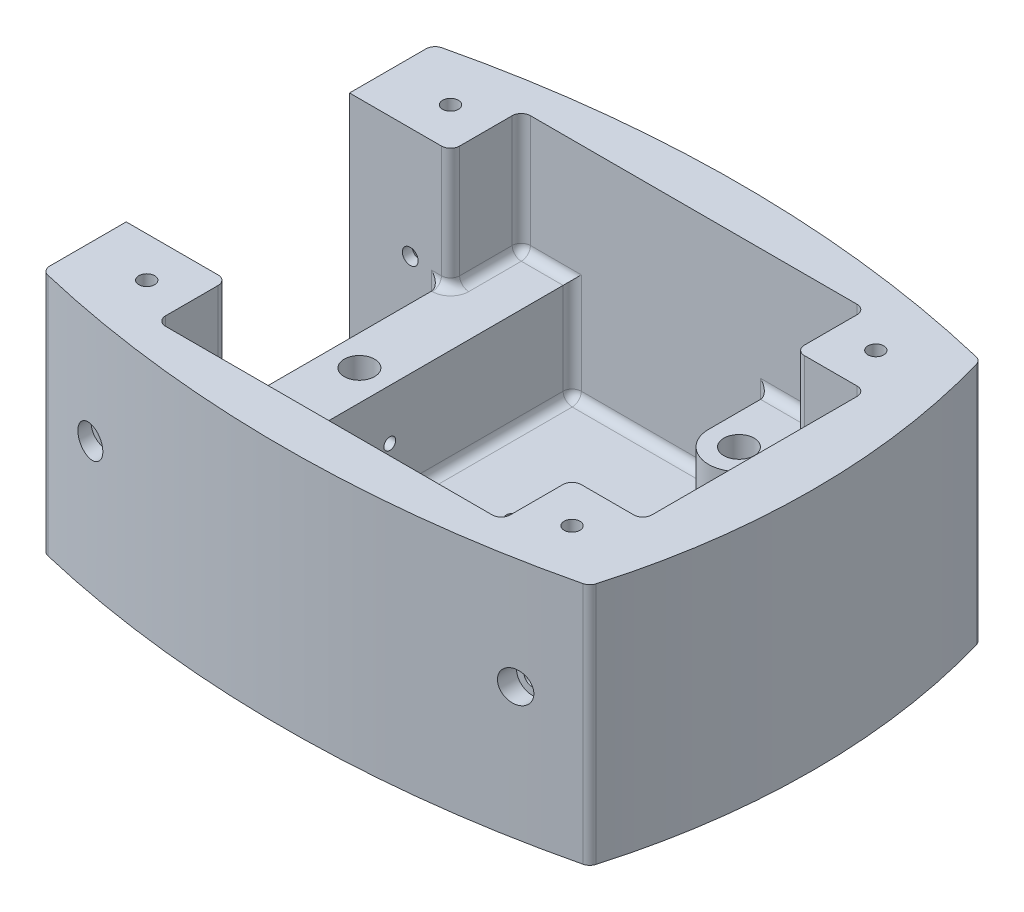
SolidWorks part; units mm, degrees
ref_plane "Front Plane" through (0, 0, 0) normal (0, 0, 1) x (1, 0, 0)
ref_plane "Top Plane" through (0, 0, 0) normal (0, 1, 0) x (1, 0, 0)
ref_plane "Right Plane" through (0, 0, 0) normal (1, 0, 0) x (0, 0, -1)
sketch "Sketch1" plane through (0, 0, 0) normal (0, 1, 0) x (1, 0, 0)
  line L0 (-140, 0) -> (0, 0) construction
  line L1 (-150.05, 10.05) -> (-129.95, 10.05)
  line L2 (-150.05, 10.05) -> (-150.05, -10.05)
  line L3 (-150.05, -10.05) -> (-129.95, -10.05)
  line L4 (-129.95, 10.05) -> (-129.95, -10.05)
  line L5 (-150.05, 10.05) -> (-129.95, -10.05) construction
  line L6 (-150.05, -10.05) -> (-129.95, 10.05) construction
  line L7 (-10.05, 10.05) -> (10.05, 10.05)
  line L8 (-10.05, 10.05) -> (-10.05, -10.05)
  line L9 (-10.05, -10.05) -> (10.05, -10.05)
  line L10 (10.05, 10.05) -> (10.05, -10.05)
  line L11 (-10.05, 10.05) -> (10.05, -10.05) construction
  line L12 (-10.05, -10.05) -> (10.05, 10.05) construction
  line L17 (-160, 14.2857) -> (-70, -50) construction
  line L18 (-150.05, -110.05) -> (-129.95, -110.05)
  line L23 (-150.05, -110.05) -> (-150.05, -89.95)
  line L24 (-150.05, -89.95) -> (-129.95, -89.95)
  line L25 (-129.95, -110.05) -> (-129.95, -89.95)
  line L26 (-150.05, -110.05) -> (-129.95, -89.95) construction
  line L27 (-150.05, -89.95) -> (-129.95, -110.05) construction
  line L28 (-10.05, -110.05) -> (10.05, -110.05)
  line L29 (-10.05, -110.05) -> (-10.05, -89.95)
  line L30 (-10.05, -89.95) -> (10.05, -89.95)
  line L31 (10.05, -110.05) -> (10.05, -89.95)
  line L32 (-10.05, -110.05) -> (10.05, -89.95) construction
  line L33 (-10.05, -89.95) -> (10.05, -110.05) construction
  line L35 (-70, -50) -> (20, -114.2857) construction
  line L37 (20, 14.2857) -> (-70, -50) construction
  line L38 (-70, -50) -> (-160, -114.2857) construction
  line L39 (-126.75, 10.05) -> (-126.75, -13.25)
  line L40 (-126.75, -13.25) -> (-150.05, -13.25)
  line L41 (-13.25, 10.05) -> (-13.25, -13.25)
  line L42 (-150.05, -86.75) -> (-126.75, -86.75)
  line L43 (-126.75, -86.75) -> (-126.75, -110.05)
  line L44 (-13.25, -13.25) -> (10.05, -13.25)
  line L45 (-13.25, -110.05) -> (-13.25, -86.75)
  line L46 (-13.25, -86.75) -> (10.05, -86.75)
  line L47 (10.05, -13.25) -> (10.05, -86.75)
  line L48 (-126.75, -110.05) -> (-13.25, -110.05)
  line L49 (-126.75, 10.05) -> (-13.25, 10.05)
  line L50 (-150.05, -13.25) -> (-150.05, -86.75)
  line L51 (-160, 14.2857) -> (-160, -114.2857)
  line L52 (-70, -50) -> (-54.5, -34.5) construction
  line L53 (-70, -50) -> (-85.5, -65.5) construction
  line L54 (-70, -50) -> (-54.5, -65.5) construction
  line L55 (-70, -50) -> (-85.5, -34.5) construction
  line L86 (-70, -50) -> (-55.1332, -66.9694) construction
  line L87 (-70, -50) -> (-55.1332, -33.0306) construction
  line L88 (-38.2949, -86.1892) -> (-35, -89.95) construction
  line L89 (-38.2949, -13.8108) -> (-35, -10.05) construction
  line L90 (-45, -89.95) -> (-45, -110.05)
  line L91 (-25, -89.95) -> (-25, -110.05)
  line L92 (-45, -10.05) -> (-45, 10.05)
  line L93 (-25, -10.05) -> (-25, 10.05)
  line L94 (-130, -13.25) -> (-130, -86.75)
  line L95 (-110, 10.05) -> (-110, -110.05)
  line L97 (-150.05, -13.25) -> (-160, -13.25)
  line L98 (-150.05, -86.75) -> (-160, -86.75)
  circle A2 centre (-120, -50) radius 5
  arc A5 (-160, 14.2857) -> (20, 14.2857) centre (-70, -354.9026) cw
  arc A6 (-160, -114.2857) -> (20, -114.2857) centre (-70, 254.9026) ccw
  arc A8 (20, 14.2857) -> (20, -114.2857) centre (-195.6208, -50) cw
  circle A9 centre (-70, -50) radius 14
  circle A10 centre (-35, -10.05) radius 5
  circle A11 centre (-35, -89.95) radius 5
  circle A16 centre (-85.5, -34.5) radius 1.6
  circle A17 centre (-54.5, -34.5) radius 1.6
  circle A18 centre (-85.5, -65.5) radius 1.6
  circle A19 centre (-54.5, -65.5) radius 1.6
  circle A20 centre (-140, 0) radius 2.6
  circle A21 centre (0, 0) radius 2.6
  circle A22 centre (0, -100) radius 2.6
  circle A23 centre (-140, -100) radius 2.6
  arc A42 (-45, -10.05) -> (-25, -10.05) centre (-35, -10.05) ccw
  arc A43 (-25, -89.95) -> (-45, -89.95) centre (-35, -89.95) ccw
  point P0 (-140, 0)
  point P5 (0, 0)
  point P10 (0, -100)
  point P16 (-140, -100)
  dimension "D4" = 28
  dimension "D5" = 31
  dimension "D7" = 225
  dimension "D8" = 380
  dimension "D9" = 10
  dimension "D16" = 3.2
  dimension "D17" = 5.2
  dimension "D19" = 10
  dimension "D18" = 20
  dimension "D20" = 10
  dimension "D1" = 20.1
  dimension "D2" = 140
  dimension "D3" = 100
  dimension "D6" = 180
  dimension "D10" = 35
  dimension "D11" = 3.2
  dimension "D12" = 3.2
  dimension "D13" = 3.2
  dimension "D14" = 3.2
  dimension "D15" = 20
extrude "Boss-Extrude1" add sketch "Sketch1" along normal blind 80 contours A8 A5 L51 A6 A9 A10 A11 A2 L31 L28 L29 L30 L25 L18 L23 L24 L1 L4 L3 L2 L7 L10 L9 L8 region at (-129.1671, 0, 1.6)
extrude "Boss-Extrude9" add sketch "Sketch1<7>" along normal blind 6.825 contours L40 L50 L42 L43 L48 L45 L46 L47 L44 L41 L49 L39 A19 A18 A17 A16 A9 | A2 | A10 | A11 | L50 | L98 L50 L97 L51 region at (-118.375, 0, -8.8325) region at (-54.8422, 0, 50) region at (-140.025, 0, 50) region at (-35, 0, 3.0299) region at (-155.025, 0, 50) region at (-35, 0, 96.9701)
sketch "Sketch1<7>" plane through (0, 0, 0) normal (0, 1, 0) x (1, 0, 0) same geometry as "Sketch1"
sketch "Sketch2" plane through (0, 0, 13.25) normal (0, 0, 1) x (1, 0, 0)
  line L0 (-150.05, 80) -> (-129.95, 80) construction
  line L1 (-126.75, 80) -> (-160, 80) construction
  line L2 (-129.95, 80) -> (-129.95, 6.825) construction
  line L3 (-150.05, 80) -> (-129.95, 6.825) construction
  line L4 (-129.95, 80) -> (-129.95, 0) construction
  line L5 (-129.95, 6.825) -> (-150.05, 6.825) construction
  line L6 (-150.05, 80) -> (-150.05, 0) construction
  line L7 (-150.05, 6.825) -> (-150.05, 80) construction
  line L8 (-10.05, 80) -> (10.05, 80) construction
  line L9 (10.05, 80) -> (10.05, 6.825) construction
  line L10 (10.05, 6.825) -> (-10.05, 6.825) construction
  line L11 (-10.05, 6.825) -> (-10.05, 80) construction
  line L12 (-129.95, 80) -> (-150.05, 6.825) construction
  line L13 (10.05, 80) -> (-10.05, 6.825) construction
  line L14 (-10.05, 80) -> (10.05, 6.825) construction
  line L15 (-126.75, 6.825) -> (-160, 6.825) construction
  circle A0 centre (-140, 43.4125) radius 2.6
  circle A2 centre (0, 43.4125) radius 2.6
  circle A5 centre (0, 43.4125) radius 5.05
  circle A6 centre (-140, 43.4125) radius 5.05
  dimension "D1" = 5.2
  dimension "D2" = 10.1
extrude "Cut-Extrude1" cut sketch "Sketch2" against normal blind 62 contours A6 A0 | A0 | A5 A2 | A2 region at (-140, 43.4125, 13.25) region at (0, 43.4125, 13.25) region at (-4.9072, 43.4125, 13.25) region at (-144.9072, 43.4125, 13.25)
extrude "Boss-Extrude5" add sketch "Sketch2<3>" against normal blind 26.5
sketch "Sketch2<3>" plane through (0, 0, 13.25) normal (0, 0, 1) x (1, 0, 0) same geometry as "Sketch2"
extrude "Cut-Extrude2" cut sketch "Sketch2<4>" against normal up to surface (23.3 mm away) up to face at (-145.05, 43.4125, -10.05)
sketch "Sketch2<4>" plane through (0, 0, 13.25) normal (0, 0, 1) x (1, 0, 0) same geometry as "Sketch2"
extrude "Boss-Extrude6" add sketch "Sketch2<5>" against normal up to surface (3.2 mm away) up to face at (-145.05, 43.4125, 10.05)
sketch "Sketch2<5>" plane through (0, 0, 13.25) normal (0, 0, 1) x (1, 0, 0) same geometry as "Sketch2"
extrude "Cut-Extrude3" cut sketch "Sketch2<6>" along normal blind 127.2 contours A6 A0 | A5 A2 | A2 | A0 region at (-140, 43.4125, 13.25) region at (0, 43.4125, 13.25) region at (-4.9072, 43.4125, 13.25) region at (-144.9072, 43.4125, 13.25)
sketch "Sketch2<6>" plane through (0, 0, 13.25) normal (0, 0, 1) x (1, 0, 0) same geometry as "Sketch2"
extrude "Boss-Extrude7" add sketch "Sketch2<7>" along normal blind 100 contours A6 A0 | A5 A2 region at (-4.9072, 43.4125, 13.25) region at (-144.9072, 43.4125, 13.25)
sketch "Sketch2<7>" plane through (0, 0, 13.25) normal (0, 0, 1) x (1, 0, 0) same geometry as "Sketch2"
extrude "Cut-Extrude4" cut sketch "Sketch2<8>" along normal up to surface (96.8 mm away) up to face at (-145.05, 43.4125, 110.05)
sketch "Sketch2<8>" plane through (0, 0, 13.25) normal (0, 0, 1) x (1, 0, 0) same geometry as "Sketch2"
extrude "Boss-Extrude8" add sketch "Sketch2<9>" along normal up to surface (76.7 mm away) up to face at (-145.05, 43.4125, 89.95)
sketch "Sketch2<9>" plane through (0, 0, 13.25) normal (0, 0, 1) x (1, 0, 0) same geometry as "Sketch2"
extrude "Cut-Extrude5" cut sketch "Sketch2<10>" along normal up to surface (73.5 mm away) contours A6 A0 | A0 | A5 A2 | A2 region at (-140, 43.4125, 13.25) region at (0, 43.4125, 13.25) region at (-4.9072, 43.4125, 13.25) region at (-144.9072, 43.4125, 13.25) up to face at (-5.05, 43.4125, 86.75)
sketch "Sketch2<10>" plane through (0, 0, 13.25) normal (0, 0, 1) x (1, 0, 0) same geometry as "Sketch2"
extrude "Boss-Extrude10" add sketch "Sketch1<9>" along normal blind 80 contours L18 L25 L24 L23 | L4 L1 L2 L3 | L28 L31 L30 L29 | L10 L7 L8 L9 region at (-140, 0, -9.7657) region at (0, 0, -9.7657) region at (-149.7657, 0, 100) region at (-9.7657, 0, 100)
sketch "Sketch1<9>" plane through (0, 0, 0) normal (0, 1, 0) x (1, 0, 0) same geometry as "Sketch1"
extrude "Cut-Extrude7" cut sketch "Sketch1<10>" along normal blind 61.9 contours L18 L25 L24 L23 | L4 L1 L2 L3 | L28 L31 L30 L29 | L10 L7 L8 L9 region at (-140, 0, -9.7657) region at (0, 0, -9.7657) region at (-149.7657, 0, 100) region at (-9.7657, 0, 100)
sketch "Sketch1<10>" plane through (0, 0, 0) normal (0, 1, 0) x (1, 0, 0) same geometry as "Sketch1"
extrude "Boss-Extrude11" add sketch "Sketch1<11>" along normal blind 40 contours A2 | A10 | A11 region at (-118.375, 0, -8.8325) region at (-35, 0, 3.0299) region at (-35, 0, 96.9701)
sketch "Sketch1<11>" plane through (0, 0, 0) normal (0, 1, 0) x (1, 0, 0) same geometry as "Sketch1"
sketch "Sketch3" plane through (-45, 0, 0) normal (-1, 0, 0) x (0, 0, 1)
  line L0 (10.05, 40) -> (10.05, 6.825) construction
  line L1 (89.95, 40) -> (89.95, 6.825) construction
  line L2 (10.05, 23.4125) -> (50, 23.4125) construction
  line L3 (50, 23.4125) -> (89.95, 23.4125) construction
  circle A0 centre (10.05, 23.4125) radius 1.95
  circle A1 centre (89.95, 23.4125) radius 1.95
  circle A2 centre (50, 23.4125) radius 1.95
  dimension "D1" = 3.9
extrude "Cut-Extrude10" cut sketch "Sketch3" against normal blind 20
extrude "Cut-Extrude11" cut sketch "Sketch3<3>" along normal blind 118 contours A2 region at (-45, 23.4125, 50)
sketch "Sketch3<3>" plane through (-45, 0, 0) normal (-1, 0, 0) x (0, 0, 1) same geometry as "Sketch3"
fillet "Fillet1" radius 3 49 edges at (-160, 40, -14.2857) (20, 40, 114.2857) (20, 40, -14.2857) (-160, 40, 114.2857) (-13.25, 43.4125, 110.05) (-13.25, 43.4125, 86.75) (10.05, 43.4125, 86.75) (10.05, 43.4125, 13.25) (-13.25, 43.4125, 13.25) (-13.25, 43.4125, -10.05) (-126.75, 60, 110.05) (-126.75, 60, 86.75) (-126.75, 60, 13.25) (-126.75, 60, -10.05) (-13.25, 6.825, 1.6) (-1.6, 6.825, 13.25) (-25, 23.4125, 110.05) (-45, 23.4125, 110.05) (-130, 23.4125, 13.25) (-130, 23.4125, 86.75) (-110, 23.4125, 110.05) (-25, 23.4125, -10.05) (-45, 23.4125, -10.05) (-110, 23.4125, -10.05) (-128.375, 40, 86.75) (-128.375, 40, 13.25) (-13.25, 6.825, 98.4) (-45, 6.825, 100) (-25, 6.825, 100) (-25, 6.825, 0) (-45, 6.825, 0) (-35, 40, 110.05) (-118.375, 40, 110.05) (-126.75, 40, 98.4) (-35, 40, -10.05) (-77.5, 6.825, 110.05) (-126.75, 40, 1.6) (-118.375, 40, -10.05) (-110, 6.825, 50) (-19.125, 6.825, -10.05) (-19.125, 6.825, 110.05) (-35, 6.825, 79.95) (-1.6, 6.825, 86.75) (10.05, 6.825, 50) (-145, 6.825, 13.25) (-145, 6.825, 86.75) (-130, 6.825, 50) (-35, 6.825, 20.05) (-77.5, 6.825, -10.05)
sketch "Sketch4" plane through (10.05, 0, 0) normal (-1, 0, 0) x (0, 0, 1)
  line L0 (22, 65) -> (78, 65) construction
  line L1 (78, 65) -> (78, 29.2) construction
  line L2 (22, 65) -> (22, 29.2) construction
  line L3 (22, 29.2) -> (78, 29.2) construction
  line L4 (22, 65) -> (78, 29.2) construction
  line L5 (78, 65) -> (22, 29.2) construction
  line L6 (16.25, 80) -> (83.75, 80) construction
  circle A0 centre (22, 65) radius 1.5
  circle A1 centre (78, 65) radius 1.5
  circle A2 centre (78, 29.2) radius 1.5
  circle A3 centre (22, 29.2) radius 1.5
  point P10 (50, 80)
  point P11 (50, 65)
  dimension "D3" = 3
  dimension "D1" = 35.8
  dimension "D2" = 56
  dimension "D4" = 15
extrude "Cut-Extrude12" cut sketch "Sketch4" against normal blind 10
